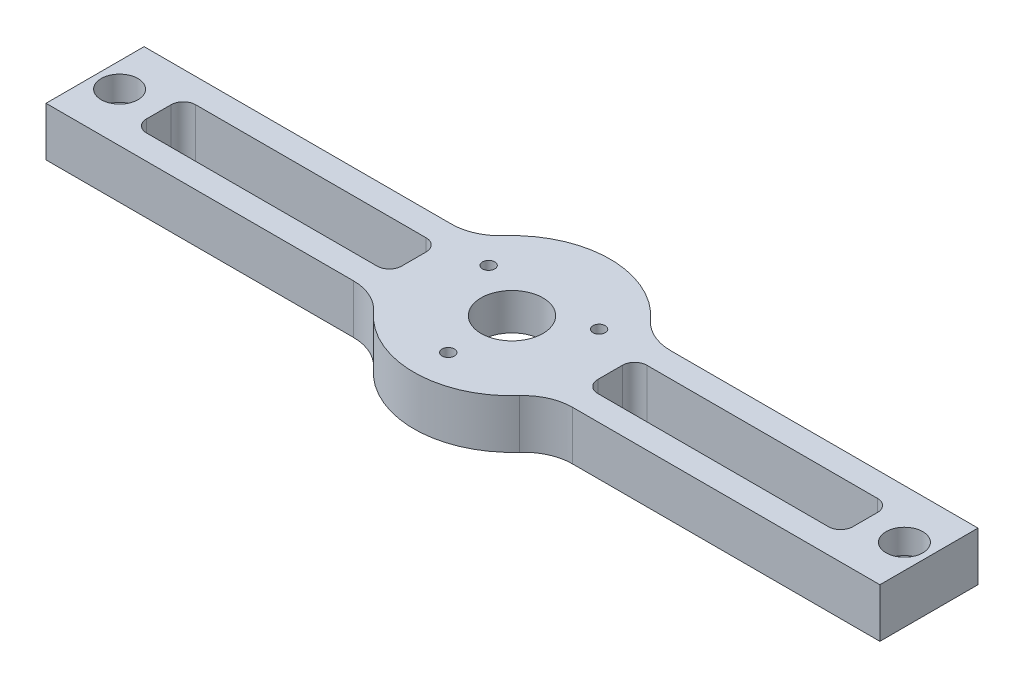
SolidWorks part; units mm, degrees
material "6061-T6 (SS)"
ref_plane "Front Plane" through (0, 0, 0) normal (0, 0, 1) x (1, 0, 0)
ref_plane "Top Plane" through (0, 0, 0) normal (0, 1, 0) x (1, 0, 0)
ref_plane "Right Plane" through (0, 0, 0) normal (1, 0, 0) x (0, 0, -1)
sketch "Sketch2" plane through (0, 0, 0) normal (0, 1, 0) x (1, 0, 0)
  line L0 (-21.997, 0) -> (0, 0) construction
  line L1 (-107.95, -25.4) -> (-21.997, -25.4)
  line L2 (-107.95, -25.4) -> (-107.95, 0)
  line L3 (-107.95, 0) -> (-21.997, 0)
  line L4 (-21.997, -25.4) -> (-21.997, 0)
  line L5 (21.997, -25.4) -> (107.95, -25.4)
  line L6 (21.997, -25.4) -> (21.997, 0)
  line L7 (21.997, 0) -> (107.95, 0)
  line L8 (107.95, -25.4) -> (107.95, 0)
  line L9 (0, 0) -> (21.997, 0) construction
  circle A0 centre (0, -12.7) radius 8.001
  circle A1 centre (0, -12.7) radius 25.4
  point P13 (107.95, -12.7)
  dimension "D3" = 215.9
  dimension "D4" = 16.002
  dimension "D5" = 50.8
  dimension "D1" = 25.4
  dimension "D2" = 25.4
extrude "Boss-Extrude1" add sketch "Sketch2" along normal blind 12.7 contours A1 L3 L2 L1 | L4 A1 | L6 A1 L4 A0 | L6 A1 | A1 L5 L8 L7 region at (-66.1179, 0, 12.7) region at (-23.3664, 0, 12.7) region at (-21.325, 0, 12.7) region at (66.1179, 0, 12.7) region at (23.3664, 0, 12.7)
fillet "Fillet1" radius 12.7 4 edges at (21.997, 6.35, 0) (21.997, 6.35, 25.4) (-21.997, 6.35, 25.4) (-21.997, 6.35, 0)
sketch "Sketch3" plane through (0, 0, 0) normal (0, -1, 0) x (1, 0, 0)
  circle A0 centre (0, 12.7) radius 22.225
  dimension "D1" = 44.45
extrude "Cut-Extrude1" cut sketch "Sketch3" against normal blind 3.175
sketch "Sketch4" plane through (0, 12.7, 0) normal (0, 1, 0) x (1, 0, 0)
  line L0 (-107.95, -25.4) -> (-107.95, 0) construction
  line L1 (107.95, -25.4) -> (107.95, 0) construction
  circle A0 centre (-101.6, -12.7) radius 4.7625
  circle A1 centre (101.6, -12.7) radius 4.7625
  point P4 (-107.95, -12.7)
  point P5 (107.95, -12.7)
  dimension "D1" = 9.525
  dimension "D2" = 9.525
  dimension "D3" = 6.35
  dimension "D4" = 6.35
extrude "Cut-Extrude2" cut sketch "Sketch4" against normal blind 6.35
sketch "Sketch5" plane through (0, 6.35, 0) normal (0, 1, 0) x (1, 0, 0)
  circle A0 centre (-101.6, -12.7) radius 3.175
  circle A1 centre (101.6, -12.7) radius 3.175
  dimension "D1" = 6.35
  dimension "D2" = 6.35
extrude "Cut-Extrude3" cut sketch "Sketch5" against normal through all
sketch "Sketch6" plane through (0, 3.175, 0) normal (0, -1, 0) x (1, 0, 0)
  circle A0 centre (0, 29.21) radius 1.5875
  circle A1 centre (0, 12.7) radius 8.001 construction
  circle A2 centre (0, 12.7) radius 8.001 construction
  circle A3 centre (14.2981, 4.445) radius 1.5875
  circle A4 centre (-14.2981, 4.445) radius 1.5875
  dimension "D2" = 3.175
  dimension "D1" = 16.51
  dimension "D3" = 3
extrude "Cut-Extrude4" cut sketch "Sketch6" against normal through all
sketch "Sketch7" plane through (0, 12.7, 0) normal (0, 1, 0) x (1, 0, 0)
  line L0 (-107.95, 0) -> (-28.3981, 0) construction
  line L1 (-91.44, -19.05) -> (-25.4, -19.05)
  line L2 (-91.44, -19.05) -> (-91.44, -6.35)
  line L3 (-91.44, -6.35) -> (-25.4, -6.35)
  line L4 (-25.4, -19.05) -> (-25.4, -6.35)
  line L5 (25.4, -19.05) -> (91.44, -19.05)
  line L6 (25.4, -19.05) -> (25.4, -6.35)
  line L7 (25.4, -6.35) -> (91.44, -6.35)
  line L8 (91.44, -19.05) -> (91.44, -6.35)
  line L9 (-107.95, -25.4) -> (-28.3981, -25.4) construction
  circle A0 centre (-101.6, -12.7) radius 4.7625 construction
  circle A1 centre (101.6, -12.7) radius 4.7625 construction
  dimension "D3" = 10.16
  dimension "D1" = 6.35
  dimension "D2" = 6.35
  dimension "D4" = 50.8
  dimension "D5" = 10.16
extrude "Cut-Extrude5" cut sketch "Sketch7" against normal through all
fillet "Fillet2" radius 3.175 8 edges at (25.4, 6.35, 6.35) (25.4, 6.35, 19.05) (91.44, 6.35, 19.05) (91.44, 6.35, 6.35) (-25.4, 6.35, 6.35) (-25.4, 6.35, 19.05) (-91.44, 6.35, 19.05) (-91.44, 6.35, 6.35)
